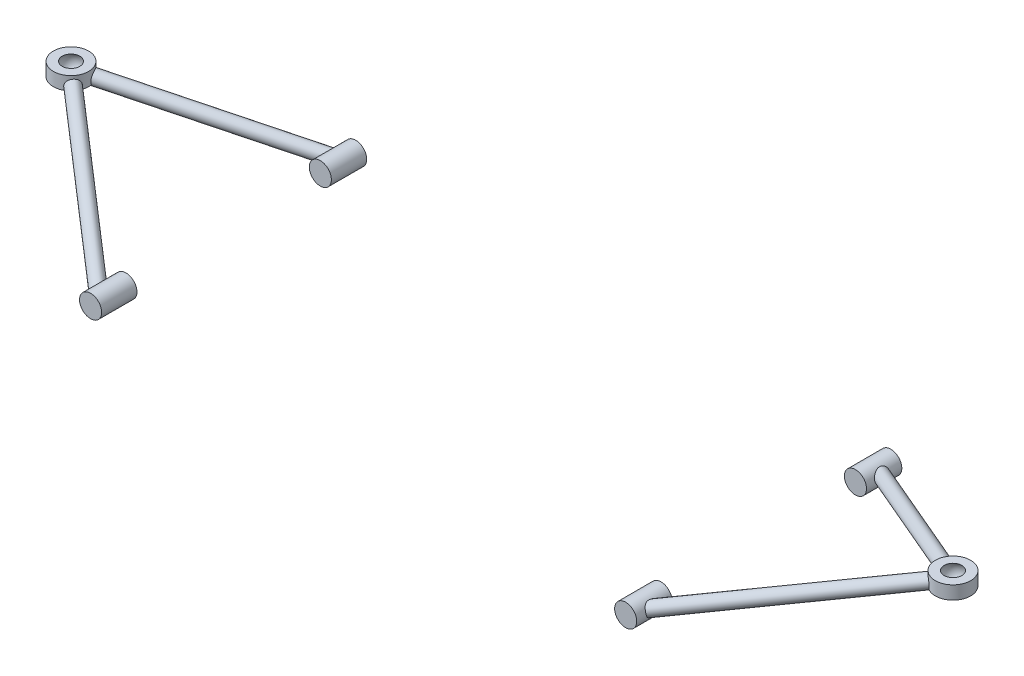
SolidWorks part; units mm, degrees
ref_plane "Front Plane" through (0, 0, 0) normal (0, 0, 1) x (1, 0, 0)
ref_plane "Top Plane" through (0, 0, 0) normal (0, 1, 0) x (1, 0, 0)
ref_plane "Right Plane" through (0, 0, 0) normal (1, 0, 0) x (0, 0, -1)
sketch "Sketch1" plane through (0, 0, -1475) normal (0, 0, -1) x (-1, 0, 0)
  circle A0 centre (-302.7695, 342.0552) radius 12.5
  dimension "D1" = 25
extrude "Boss-Extrude1" add sketch "Sketch1" along normal up to surface (40 mm away)
sketch "Sketch2" plane through (0, 0, -1735) normal (0, 0, -1) x (-1, 0, 0)
  circle A0 centre (-302.7695, 342.0552) radius 12.5
  dimension "D1" = 25
extrude "Boss-Extrude2" add sketch "Sketch2" along normal up to surface (40 mm away) separate body
ref_plane "Plane4" through (0, 389.2368, 0) normal (0, 1, 0) x (1, 0, 0)
sketch "Sketch3" plane through (0, 389.2368, 0) normal (0, 1, 0) x (1, 0, 0)
  line L0 (499.0542, 1661.6367) -> (499.0542, 1636.6367) construction
  circle A0 centre (499.0542, 1649.1367) radius 20
  circle A1 centre (499.0542, 1649.1367) radius 12.5
  point P7 (499.0542, 1649.1367)
  dimension "D1" = 40
  dimension "D2" = 25
extrude "Boss-Extrude3" add sketch "Sketch3" along normal mid plane 15 separate body contours L0 A1 | A1 L0 | A0 A1 region at (504.3593, 389.2368, -1649.1367) region at (493.749, 389.2368, -1649.1367) region at (479.6198, 389.2368, -1649.1367)
sketch3d "3DSketch1"
  line L0 (302.7695, 342.0552, -1515) -> (302.7695, 342.0552, -1475) construction
  line L1 (302.7695, 342.0552, -1515) -> (302.7695, 342.0552, -1475) construction
  line L2 (302.7695, 342.0552, -1735) -> (302.7695, 342.0552, -1775)
  line L3 (302.7695, 342.0552, -1775) -> (302.7695, 342.0552, -1735) construction
  line L4 (302.7695, 342.0552, -1730) -> (302.7695, 342.0552, -1735) construction
sketch3d "3DSketch2"
  line L0 (302.7695, 342.0552, -1485) -> (499.0542, 389.2368, -1649.1367)
  line L2 (499.0542, 389.2368, -1649.1367) -> (302.7695, 342.0552, -1760)
  line L4 (302.7695, 342.0552, -1515) -> (302.7695, 342.0552, -1475) construction
  line L5 (302.7695, 342.0552, -1735) -> (302.7695, 342.0552, -1775) construction
  dimension "D1" = 10
  dimension "D2" = 15
sweep "Sweep1" add path "3DSketch2" circular profile diameter 15 parameters "D3"=15
revolve "Cut-Revolve1" cut sketch "Sketch3<3>" angle 360 about L0 region at (493.749, 389.2368, -1649.1367)
sketch "Sketch3<3>" plane through (0, 389.2368, 0) normal (0, 1, 0) x (1, 0, 0) same geometry as "Sketch3"
mirror "Mirror2" about plane through (0, 0, 0) normal (1, 0, 0) of bodies 106
